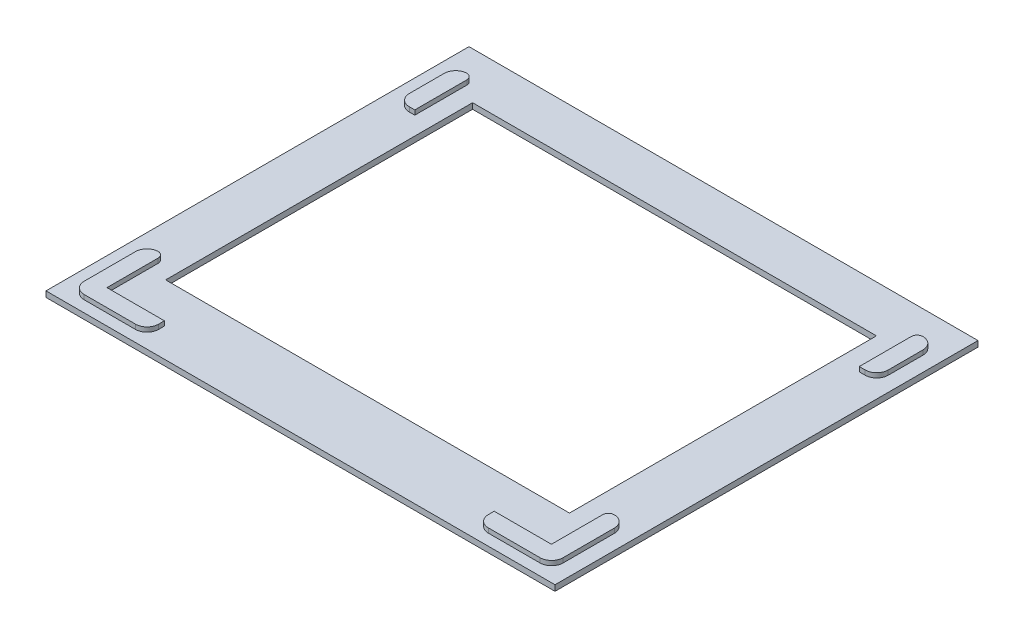
SolidWorks part; units mm, degrees
ref_plane "Front Plane" through (0, 0, 0) normal (0, 0, 1) x (1, 0, 0)
ref_plane "Top Plane" through (0, 0, 0) normal (0, 1, 0) x (1, 0, 0)
ref_plane "Right Plane" through (0, 0, 0) normal (1, 0, 0) x (0, 0, -1)
sketch "Sketch2" plane through (0, 0, 0) normal (0, 1, 0) x (1, 0, 0)
  line L1 (-56.3563, -46.8312) -> (56.3562, -46.8312)
  line L2 (-56.3563, -46.8312) -> (-56.3563, 46.8312)
  line L3 (-56.3563, 46.8312) -> (56.3562, 46.8312)
  line L4 (56.3562, -46.8312) -> (56.3562, 46.8312)
  line L5 (-56.3563, -46.8312) -> (56.3562, 46.8312) construction
  line L6 (-56.3563, 46.8312) -> (56.3562, -46.8312) construction
  line L7 (-49.2125, -40.4813) -> (49.2125, -40.4813)
  line L8 (-49.2125, -40.4813) -> (-49.2125, 40.4812)
  line L9 (-49.2125, 40.4812) -> (49.2125, 40.4812)
  line L10 (49.2125, -40.4813) -> (49.2125, 40.4812)
  line L11 (-49.2125, -40.4813) -> (49.2125, 40.4812) construction
  line L12 (-49.2125, 40.4812) -> (49.2125, -40.4813) construction
  line L13 (-54.7688, -45.5121) -> (54.7687, -45.5121)
  line L14 (-54.7688, -45.5121) -> (-54.7688, 45.5121)
  line L15 (-54.7688, 45.5121) -> (54.7687, 45.5121)
  line L16 (54.7687, -45.5121) -> (54.7687, 45.5121)
  line L17 (-54.7688, -45.5121) -> (54.7687, 45.5121) construction
  line L18 (-54.7688, 45.5121) -> (54.7687, -45.5121) construction
  line L19 (-45.2125, -31.4813) -> (44.2125, -31.4813)
  line L20 (-45.2125, -31.4813) -> (-45.2125, 36.4812)
  line L21 (-45.2125, 36.4812) -> (44.2125, 36.4812)
  line L22 (44.2125, -31.4813) -> (44.2125, 36.4812)
  line L23 (-45.2125, -31.4813) -> (44.2125, 36.4812) construction
  line L24 (-45.2125, 36.4812) -> (44.2125, -31.4813) construction
  line L25 (-49.2125, 40.4812) -> (-52.9603, 40.4812)
  line L26 (-49.2125, 40.4812) -> (-49.2125, 27.6816)
  line L27 (-49.2125, 27.6816) -> (-52.9603, 27.6816)
  line L28 (-52.9603, 40.4812) -> (-52.9603, 27.6816)
  line L29 (49.2125, 40.4812) -> (53.0754, 40.4812)
  line L30 (49.2125, 40.4812) -> (49.2125, 27.6816)
  line L31 (49.2125, 27.6816) -> (53.0754, 27.6816)
  line L32 (53.0754, 40.4812) -> (53.0754, 27.6816)
  line L33 (-49.2125, -40.4813) -> (-52.9603, -40.4813)
  line L34 (-49.2125, -40.4813) -> (-49.2125, -27.8702)
  line L35 (-49.2125, -27.8702) -> (-52.9603, -27.8702)
  line L36 (-52.9603, -40.4813) -> (-52.9603, -27.8702)
  line L37 (-52.9603, -40.4813) -> (-36.4916, -40.4813)
  line L38 (-52.9603, -40.4813) -> (-52.9603, -44.3186)
  line L39 (-52.9603, -44.3186) -> (-36.4916, -44.3186)
  line L40 (-36.4916, -40.4813) -> (-36.4916, -44.3186)
  line L41 (49.2125, -40.4813) -> (53.0754, -40.4813)
  line L42 (49.2125, -40.4813) -> (49.2125, -27.8702)
  line L43 (49.2125, -27.8702) -> (53.0754, -27.8702)
  line L44 (53.0754, -40.4813) -> (53.0754, -27.8702)
  line L45 (53.0754, -40.4813) -> (36.5379, -40.4813)
  line L46 (53.0754, -40.4813) -> (53.0754, -44.3186)
  line L47 (53.0754, -44.3186) -> (36.5379, -44.3186)
  line L48 (36.5379, -40.4813) -> (36.5379, -44.3186)
  point P0 (0, 0)
  point P6 (0, 0)
  point P11 (0, 0)
  point P16 (-0.5, 2.5)
  dimension "D1" = 112.7125
  dimension "D2" = 93.6625
  dimension "D3" = 98.425
  dimension "D4" = 80.9625
  dimension "D5" = 109.5375
  dimension "D6" = 4
  dimension "D7" = 4
  dimension "D8" = 5
  dimension "D9" = 9
extrude "Boss-Extrude2" add sketch "Sketch2" along normal blind 1.016 contours L25 L28 L27 L8 | L36 L33 L8 L35 | L40 L7 L33 L38 L39 | L7 L48 L47 L46 L41 | L41 L44 L43 L10 | L32 L29 L10 L31 region at (-51.0864, 0, 34.1757) region at (-44.726, 0, 42.3999) region at (44.8067, 0, 42.3999) region at (-51.0864, 0, -34.0814) region at (51.144, 0, 34.1757) region at (51.144, 0, -34.0814)
extrude "Boss-Extrude14" add sketch "Sketch2<7>" against normal blind 1.27 contours L3 L4 L1 L2
sketch "Sketch2<7>" plane through (0, 0, 0) normal (0, 1, 0) x (1, 0, 0) same geometry as "Sketch2"
extrude "Cut-Extrude4" cut sketch "Sketch2<8>" against normal blind 1.27 contours L19 L22 L21 L20 region at (-0.5, 0, -2.5)
sketch "Sketch2<8>" plane through (0, 0, 0) normal (0, 1, 0) x (1, 0, 0) same geometry as "Sketch2"
fillet "Fillet5" radius 2.54 2 edges at (-52.9603, 0.508, -27.6816) (-52.9603, 0.508, -40.4812)
fillet "Fillet6" radius 2.54 2 edges at (53.0754, 0.508, -27.6816) (53.0754, 0.508, -40.4812)
fillet "Fillet7" radius 2.54 3 edges at (-52.9603, 0.508, 27.8702) (-52.9603, 0.508, 44.3186) (-36.4916, 0.508, 44.3186)
fillet "Fillet8" radius 2.54 3 edges at (36.5379, 0.508, 44.3186) (53.0754, 0.508, 44.3186) (53.0754, 0.508, 27.8702)
fillet "Fillet9" radius 1.27 1 edges at (-49.2125, 0.508, 27.8702)
fillet "Fillet10" radius 1.27 1 edges at (-49.2125, 0.508, -40.4812)
fillet "Fillet11" radius 1.27 1 edges at (49.2125, 0.508, 27.8702)
fillet "Fillet12" radius 1.27 1 edges at (49.2125, 0.508, -40.4812)
